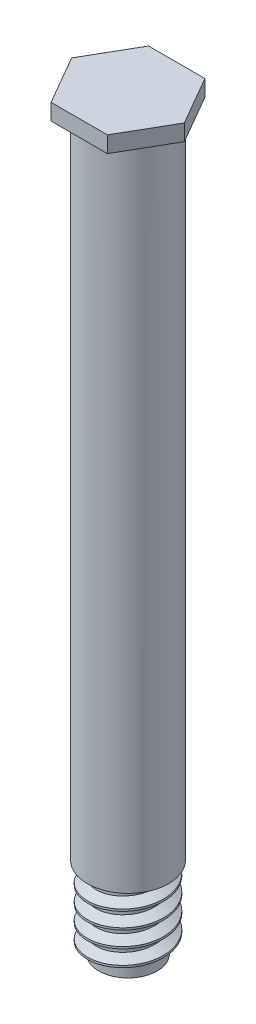
SolidWorks part; units mm, degrees
material "Alumina"
ref_plane "Front Plane" through (0, 0, 0) normal (0, 0, 1) x (1, 0, 0)
ref_plane "Top Plane" through (0, 0, 0) normal (0, 1, 0) x (1, 0, 0)
ref_plane "Right Plane" through (0, 0, 0) normal (1, 0, 0) x (0, 0, -1)
sketch "Sketch1" plane through (0, 0, 0) normal (0, 1, 0) x (1, 0, 0)
  circle A0 centre (0, 0) radius 3.175
  dimension "D1" = 6.35
extrude "Boss-Extrude1" add sketch "Sketch1" along normal blind 57.15
sketch "Sketch2" plane through (0, 57.15, 0) normal (0, 1, 0) x (1, 0, 0)
  line L1 (2.1997, -3.81) -> (4.3994, 0)
  line L2 (4.3994, 0) -> (2.1997, 3.81)
  line L3 (2.1997, 3.81) -> (-2.1997, 3.81)
  line L4 (-2.1997, 3.81) -> (-4.3994, 0)
  line L5 (-4.3994, 0) -> (-2.1997, -3.81)
  line L6 (-2.1997, -3.81) -> (2.1997, -3.81)
  circle A0 centre (0, 0) radius 3.81 construction
  dimension "D1" = 7.62
extrude "Boss-Extrude2" add sketch "Sketch2" along normal blind 1.27
sketch "Sketch6" plane through (0, 0, 0) normal (0, -1, 0) x (1, 0, 0)
  circle A0 centre (0, 0) radius 3.175
  circle A1 centre (0, 0) radius 2.286
  dimension "D1" = 6.35
  dimension "D2" = 4.572
extrude "Cut-Extrude1" cut sketch "Sketch6" against normal blind 6.35
thread "Thread3" pitch 1.27 method extrude profile "Thread Profile3" start angle 0, offset 0, length 5.334, pitch 1.27, diameter 4.572
ref_plane "Plane3" through (-2.286, 6.35, 0) normal (0, 0, 1) x (-1, 0, 0)
sketch "Thread Profile3" plane through (-2.286, 6.35, 0) normal (0, 0, 1) x (-1, 0, 0)
  line L0 (0, 0) -> (0, 1.27) construction
  line L1 (0, 0) -> (0.6874, 0.3969)
  line L2 (0.6874, 0.3969) -> (0.6874, 0.5556)
  line L3 (0.6874, 0.5556) -> (0, 0.9525)
  line L4 (0.6874, 0.4762) -> (0, 0.4762) construction
  line L11 (0, 0) -> (0, 0.9525)
  point P2 (0, 0)
  dimension "Pitch" = 1.27
  dimension "Profile_Angle" = 60
  dimension "Profile_Land" = 0.1588
  dimension "Profile_Height" = 0.6874
